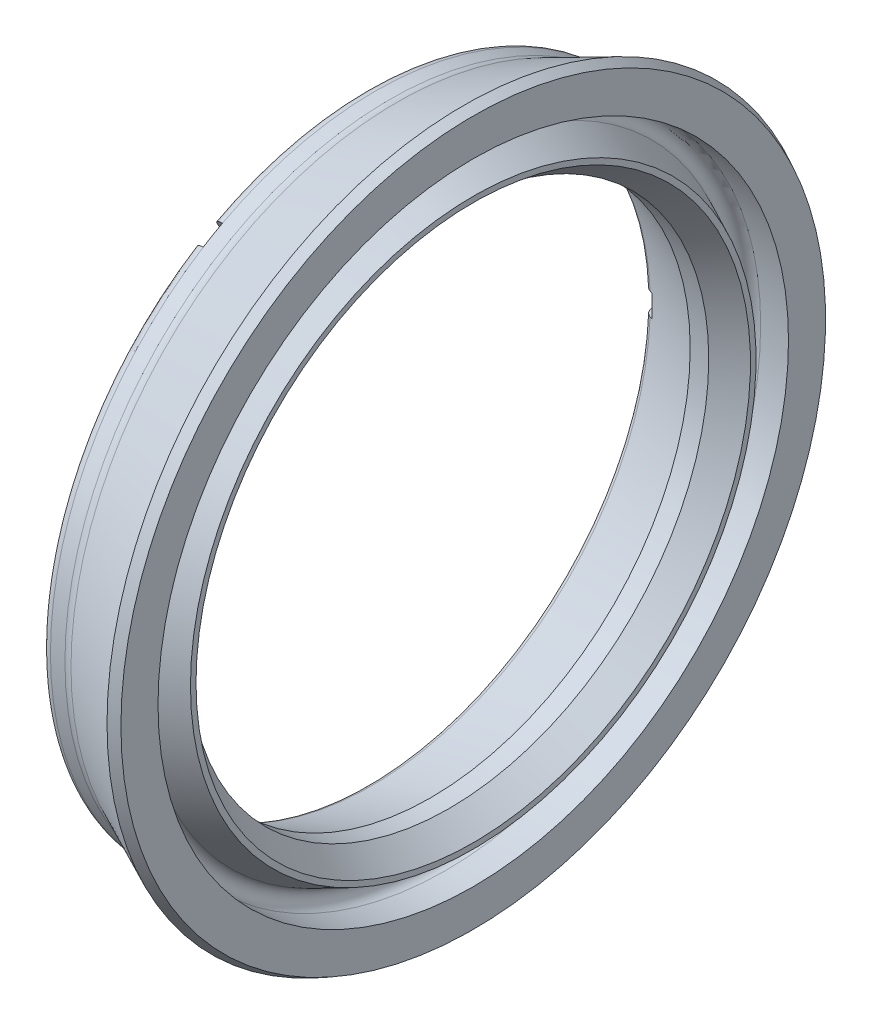
SolidWorks part; units mm, degrees
material "PU93A"
ref_plane "Front Plane" through (0, 0, 0) normal (0, 0, 1) x (1, 0, 0)
ref_plane "Top Plane" through (0, 0, 0) normal (0, 1, 0) x (1, 0, 0)
ref_plane "Right Plane" through (0, 0, 0) normal (1, 0, 0) x (0, 0, -1)
sketch "Sketch1" plane through (0, 0, 0) normal (0, 0, 1) x (1, 0, 0)
  line L0 (0, 0) -> (14.7227, 0) construction
  line L1 (0, 15.4766) -> (0, 17)
  line L2 (0.5, 17.5) -> (1.5, 17.5)
  line L3 (1.5, 17.5) -> (5.3, 19.25)
  line L4 (5.8, 19) -> (5.8, 17)
  line L5 (5.8, 17) -> (4.3, 17)
  line L6 (4.5, 14) -> (3.5, 14)
  line L7 (4.0889, 16.0467) -> (5.8, 15.25)
  line L8 (3.5, 14) -> (0.3488, 15)
  line L9 (5.8, 15.25) -> (5.8, 14.95)
  line L10 (5.8, 14.95) -> (4.5, 14)
  line L12 (5.8, 19) -> (5.3, 19.25)
  arc A0 (4.3, 17) -> (4.0889, 16.0467) centre (4.3, 16.5) ccw
  arc A1 (0.3488, 15) -> (0, 15.4766) centre (0.5, 15.4766) cw
  arc A2 (0, 17) -> (0.5, 17.5) centre (0.5, 17) cw
  dimension "D10" = 35
  dimension "D17" = 0.5
  dimension "D18" = 1
  dimension "D19" = 0.5
  dimension "D4" = 4.5
  dimension "D5" = 38.5
  dimension "D15" = 24.968
  dimension "D2" = 30
  dimension "D3" = 5.8
  dimension "D6" = 30.5
  dimension "D7" = 2
  dimension "D8" = 34
  dimension "D9" = 1.5
  dimension "D11" = 1.8035
  dimension "D12" = 0.5
  dimension "D13" = 28
  dimension "D14" = 33
  dimension "D16" = 1.5
  dimension "D20" = 0.3
revolve "Revolve1" add sketch "Sketch1" angle 360 about L0
fillet "Fillet1" radius 1 1 edges at (1.5, 0, 17.5)
sketch "Sketch2" plane through (0, 0, 0) normal (-1, 0, 0) x (0, 0, 1)
  arc A0 (-15.7873, 0.6342) -> (15.6077, 2.4577) centre (0, 0) cw construction
  text T0 "RLN TSS  28 36 6.3" font "Century Gothic" height 0.8
  dimension "D1" = 15.8
extrude "Cut-Extrude1" cut sketch "Sketch2" against normal blind 0.1
sketch "Sketch3" plane through (0, 0, 0) normal (0, 0, 1) x (1, 0, 0)
  line L1 (-0.5, 0.6) -> (0.5, 0.6)
  line L2 (-0.5, 0.6) -> (-0.5, -0.6)
  line L3 (-0.5, -0.6) -> (0.5, -0.6)
  line L4 (0.5, 0.6) -> (0.5, -0.6)
  line L5 (-0.5, 0.6) -> (0.5, -0.6) construction
  line L6 (-0.5, -0.6) -> (0.5, 0.6) construction
  point P0 (0, 0)
  dimension "D1" = 0.5
  dimension "D2" = 1.2
extrude "Cut-Extrude2" cut sketch "Sketch3" against normal through all contours L3 L4 L1 L2
pattern_circular "CirPattern1" count 3 over 360 about axis through (0.5, 0, 0) along (-1, 0, 0) of "Cut-Extrude2"
